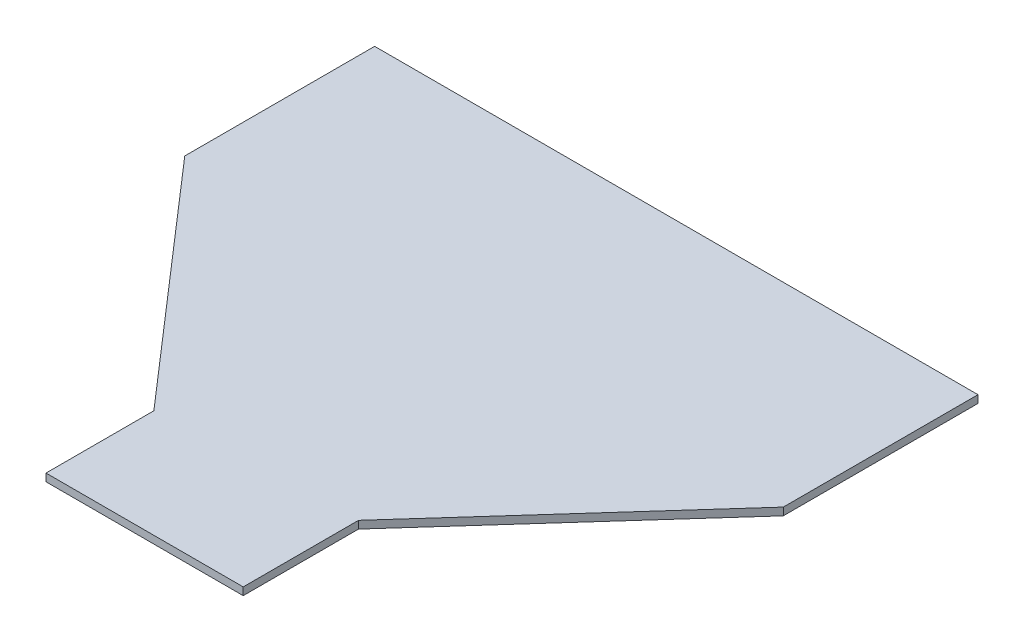
SolidWorks part; units mm, degrees
ref_plane "Front Plane" through (0, 0, 0) normal (0, 0, 1) x (1, 0, 0)
ref_plane "Top Plane" through (0, 0, 0) normal (0, 1, 0) x (1, 0, 0)
ref_plane "Right Plane" through (0, 0, 0) normal (1, 0, 0) x (0, 0, -1)
sketch "Sketch1" plane through (0, 0, 0) normal (0, 1, 0) x (1, 0, 0)
  line L5 (-17.1012, 62.0267) -> (-17.1012, 42.0267)
  line L6 (-44.1194, 42.0267) -> (-44.1194, 17.0267)
  line L7 (35.3139, 42.0267) -> (35.3139, 16.3953)
  line L8 (-44.1194, 42.0267) -> (-17.1012, 42.0267)
  line L9 (-44.1194, 17.0267) -> (-4.7603, -28.2597)
  line L10 (8.8624, 62.0267) -> (8.8624, 42.0267)
  line L11 (8.8624, 42.0267) -> (35.3139, 42.0267)
  line L12 (8.8624, 62.0267) -> (-17.1012, 62.0267)
  line L13 (35.3139, 16.3953) -> (-4.7603, -28.2597)
extrude "Boss-Extrude1" add sketch "Sketch1" along normal blind 1
sketch "Sketch2" plane through (0, 1, 0) normal (0, 1, 0) x (1, 0, 0)
  line L0 (8.8624, -28.2597) -> (-17.1012, -28.2597)
  line L2 (8.8624, 62.0267) -> (8.8624, -28.2597)
  line L3 (-17.1012, 42.0267) -> (-17.1012, -28.2597)
  line L4 (-17.1012, 42.0267) -> (8.8624, 62.0267)
extrude "Boss-Extrude2" add sketch "Sketch2" against normal blind 1
sketch "Sketch3" plane through (0, 1, 0) normal (0, 1, 0) x (1, 0, 0)
  line L1 (-17.1012, 42.0267) -> (24.714, 42.0267)
  line L2 (-17.1012, 42.0267) -> (-17.1012, 71.7124)
  line L3 (-17.1012, 71.7124) -> (24.714, 71.7124)
  line L4 (24.714, 42.0267) -> (24.714, 71.7124)
extrude "Cut-Extrude1" cut sketch "Sketch3" against normal blind 10
